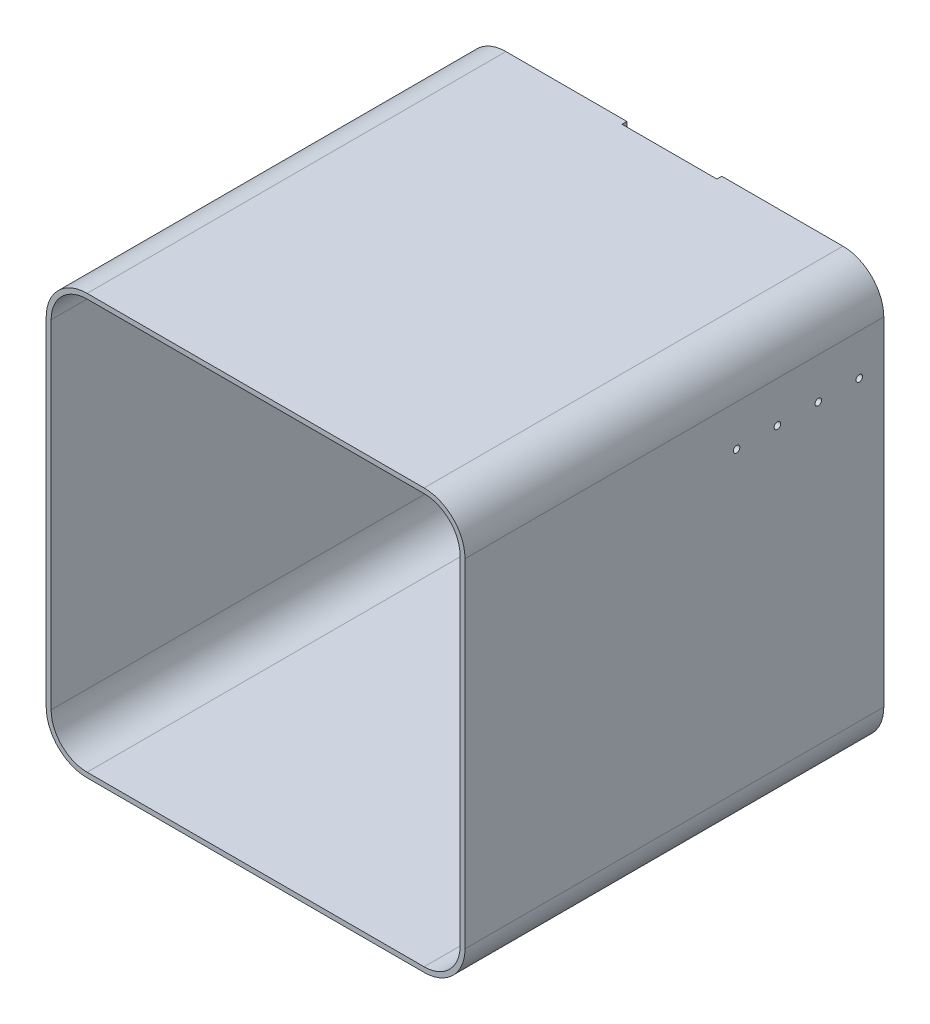
SolidWorks part; units mm, degrees
material "Pine"
ref_plane "Front Plane" through (0, 0, 0) normal (0, 0, 1) x (1, 0, 0)
ref_plane "Top Plane" through (0, 0, 0) normal (0, 1, 0) x (1, 0, 0)
ref_plane "Right Plane" through (0, 0, 0) normal (1, 0, 0) x (0, 0, -1)
sketch "Sketch1" plane through (0, 0, 0) normal (0, 0, 1) x (1, 0, 0)
  line L1 (44, 0) -> (456, 0)
  line L2 (0, 44) -> (0, 457)
  line L3 (44, 501) -> (456, 501)
  line L4 (500, 44) -> (500, 457)
  arc A0 (0, 457) -> (44, 501) centre (44, 457) cw
  arc A1 (456, 501) -> (500, 457) centre (456, 457) cw
  arc A2 (456, 0) -> (500, 44) centre (456, 44) ccw
  arc A3 (44, 0) -> (0, 44) centre (44, 44) cw
  point P9 (0, 501)
  point P12 (500, 501)
  point P15 (500, 0)
  point P18 (0, 0)
  dimension "D3" = 44
  dimension "D4" = 44
  dimension "D5" = 44
  dimension "D6" = 44
  dimension "D1" = 500
  dimension "D2" = 501
extrude "Extrude-Thin1" add sketch "Sketch1" against normal blind 512 thin contours A0 L3 A1 L4 A2 L1 A3 L2 thin type one direction wall 6
sketch "Sketch3" plane through (506, 0, 0) normal (1, 0, 0) x (0, 0, -1)
  line L0 (512, 44) -> (512, 457) construction
  line L1 (512, 457) -> (0, 457) construction
  circle A0 centre (482, 407) radius 4
  dimension "D1" = 30
  dimension "D2" = 8
  dimension "D3" = 50
extrude "Cut-Extrude1" cut sketch "Sketch3" against normal blind 10
pattern_linear "LPattern1" count 4 spacing 50 along (0, 0, 1) of "Cut-Extrude1"
sketch "Sketch4" plane through (0, 0, -512) normal (0, 0, -1) x (-1, 0, 0)
  line L0 (-44, 507) -> (-456, 507) construction
  line L1 (-44, 501) -> (-456, 501) construction
  line L2 (-308, 507) -> (-192, 507)
  line L3 (-308, 507) -> (-308, 501)
  line L4 (-308, 501) -> (-192, 501)
  line L5 (-192, 507) -> (-192, 501)
  dimension "D1" = 6
  dimension "D2" = 148
  dimension "D3" = 148
extrude "Cut-Extrude2" cut sketch "Sketch4" against normal blind 6
